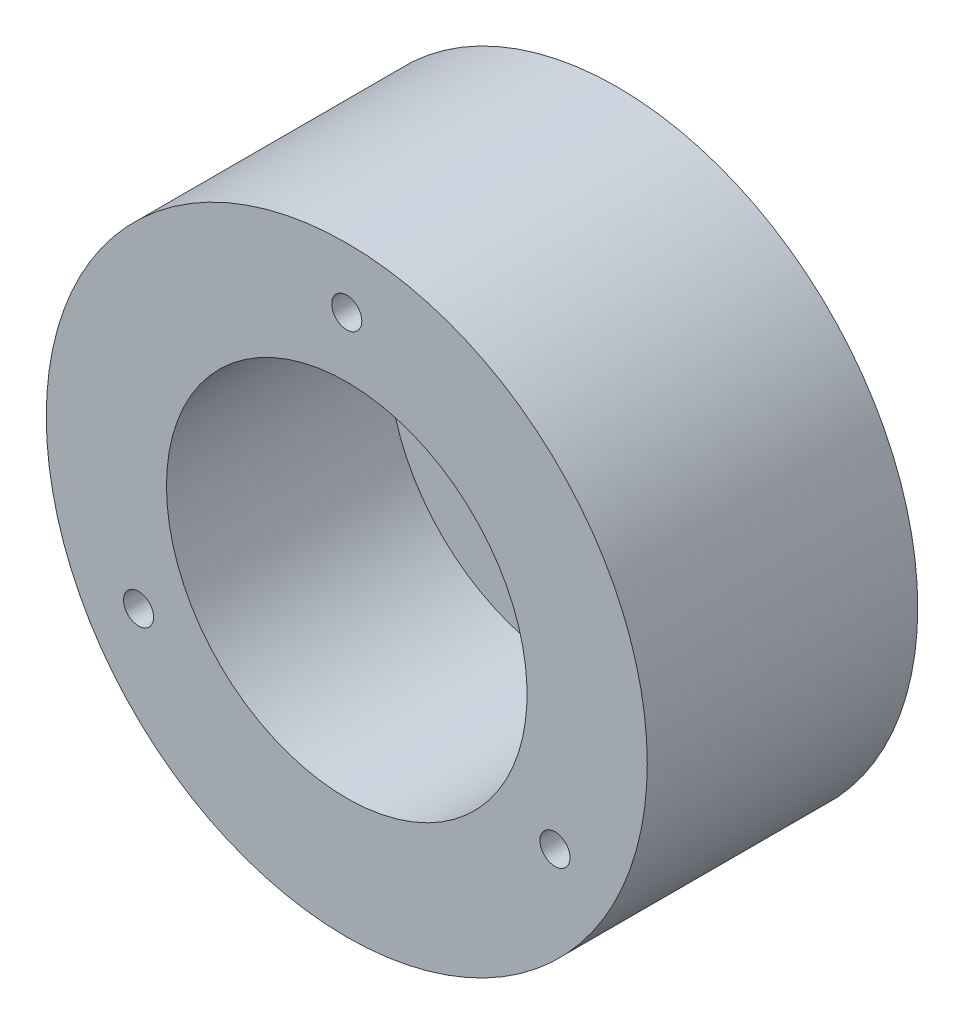
SolidWorks part; units mm, degrees
ref_plane "Front Plane" through (0, 0, 0) normal (0, 0, 1) x (1, 0, 0)
ref_plane "Top Plane" through (0, 0, 0) normal (0, 1, 0) x (1, 0, 0)
ref_plane "Right Plane" through (0, 0, 0) normal (1, 0, 0) x (0, 0, -1)
sketch "Sketch1" plane through (0, 0, 0) normal (0, 0, 1) x (1, 0, 0)
  circle A0 centre (0, 0) radius 50
  circle A1 centre (0, 0) radius 16
  dimension "D1" = 100
extrude "Boss-Extrude1" add sketch "Sketch1" along normal blind 8
sketch "Sketch2" plane through (0, 0, 8) normal (0, 0, 1) x (1, 0, 0)
  circle A0 centre (0, 0) radius 50
  circle A1 centre (0, 0) radius 30
  dimension "D1" = 20
  dimension "D2" = 100
extrude "Boss-Extrude2" add sketch "Sketch2" along normal up to surface (37 mm away) up to face at (50, 0, 0)
sketch "Sketch3" plane through (0, 0, 45) normal (0, 0, 1) x (1, 0, 0)
  circle A0 centre (0, 40) radius 2.5
  circle A1 centre (34.641, -20) radius 2.5
  circle A2 centre (-34.641, -20) radius 2.5
extrude "Cut-Extrude1" cut sketch "Sketch3" against normal through all
sketch "Sketch4" plane through (0, 0, 8) normal (0, 0, 1) x (1, 0, 0)
  circle A0 centre (0, 20) radius 2.5
  circle A1 centre (20, 0) radius 2.5
  circle A2 centre (0, -20) radius 2.5
  circle A3 centre (-20, 0) radius 2.5
  dimension "D1" = 5
  dimension "D2" = 4
extrude "Cut-Extrude2" cut sketch "Sketch4" against normal through all
